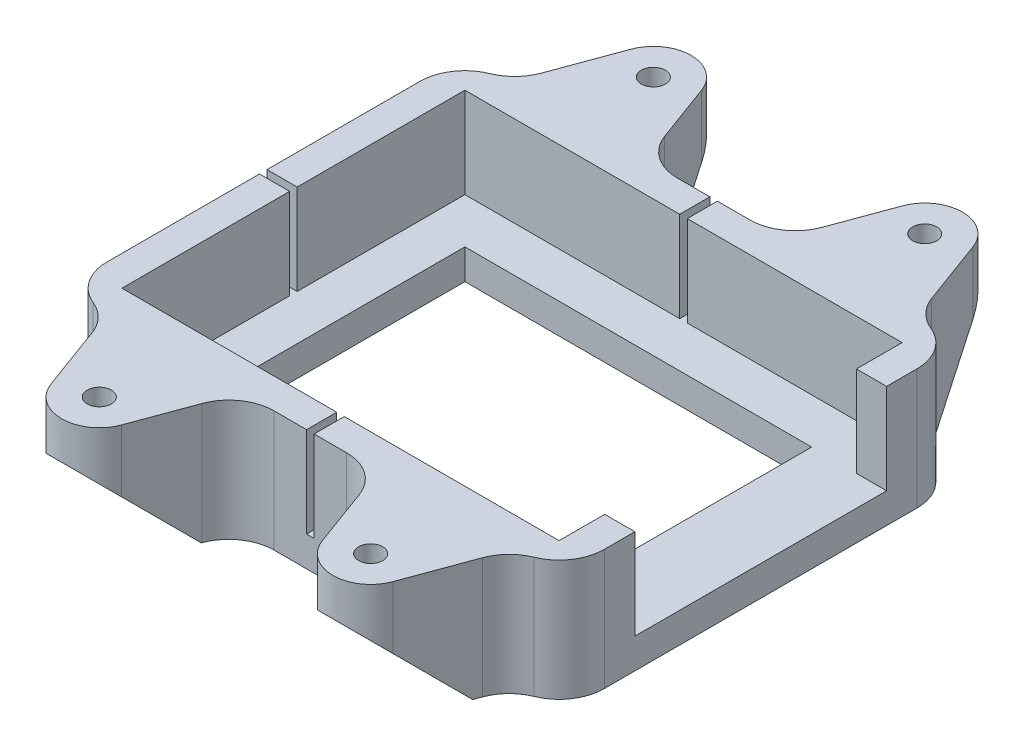
SolidWorks part; units mm, degrees
ref_plane "前视基准面" through (0, 0, 0) normal (0, 0, 1) x (1, 0, 0)
ref_plane "上视基准面" through (0, 0, 0) normal (0, 1, 0) x (1, 0, 0)
ref_plane "右视基准面" through (0, 0, 0) normal (1, 0, 0) x (0, 0, -1)
other "Configuration Table"
sketch "草图1" plane through (0, 0, 0) normal (0, 1, 0) x (1, 0, 0)
  line L0 (-33, 49.5) -> (33, 49.5)
  line L1 (-29, 45.5) -> (29, 45.5)
  line L2 (-29, 45.5) -> (-29, 0)
  line L3 (-29, 0) -> (29, 0)
  line L4 (29, 45.5) -> (29, 0)
  line L5 (33, 49.5) -> (33, -4)
  line L6 (-33, -4) -> (33, -4)
  line L7 (-33, 49.5) -> (-33, -4)
  line L8 (-23, 39.5) -> (23, 39.5)
  line L9 (23, 39.5) -> (23, 6)
  line L10 (-23, 6) -> (23, 6)
  line L11 (-23, 39.5) -> (-23, 6)
  point P4 (0, 0)
  dimension "D1" = 58
  dimension "D2" = 45.5
  dimension "D3" = 4
  dimension "D4" = 6
extrude "凸台-拉伸1" add sketch "草图1" along normal blind 4 contours L0 L7 L6 L5 L1 L4 L3 L2 | L4 L1 L2 L3 L11 L8 L9 L10 region at (0, 0, -48.6504) region at (0, 0, -44.7628)
extrude "凸台-拉伸2" add sketch "草图1<4>" along normal blind 12 from surface contours L0 L7 L6 L5 L1 L4 L3 L2 region at (0, 0, -48.6504) starting at face at (0, 4, -22.75)
sketch "草图1<4>" plane through (0, 0, 0) normal (0, 1, 0) x (1, 0, 0) same geometry as "草图1"
sketch "草图2" plane through (0, 16, 0) normal (0, 1, 0) x (1, 0, 0)
  line L0 (0, 49.5) -> (0, 0) construction
  line L1 (33, 49.5) -> (-33, 49.5) construction
  line L2 (29, 0) -> (-29, 0) construction
  line L3 (-33, 22.75) -> (33, 22.75) construction
  line L4 (-33, -4) -> (-33, 49.5) construction
  line L5 (33, -4) -> (33, 49.5) construction
  line L6 (13.3066, 61.224) -> (9, 49.5)
  line L7 (9, 49.5) -> (27, 49.5)
  line L8 (27, 49.5) -> (22.6934, 61.224)
  line L9 (-27, 49.5) -> (-22.6934, 61.224)
  line L10 (-9, 49.5) -> (-27, 49.5)
  line L11 (-13.3066, 61.224) -> (-9, 49.5)
  line L12 (-13.3066, -15.724) -> (-9, -4)
  line L13 (-9, -4) -> (-27, -4)
  line L14 (-27, -4) -> (-22.6934, -15.724)
  line L15 (27, -4) -> (22.6934, -15.724)
  line L16 (9, -4) -> (27, -4)
  line L17 (13.3066, -15.724) -> (9, -4)
  circle A1 centre (18, 59.5) radius 1.6
  arc A3 (22.6934, 61.224) -> (13.3066, 61.224) centre (18, 59.5) ccw
  arc A4 (-22.6934, 61.224) -> (-13.3066, 61.224) centre (-18, 59.5) cw
  circle A5 centre (-18, 59.5) radius 1.6
  circle A6 centre (-18, -14) radius 1.6
  arc A7 (-22.6934, -15.724) -> (-13.3066, -15.724) centre (-18, -14) ccw
  arc A8 (22.6934, -15.724) -> (13.3066, -15.724) centre (18, -14) cw
  circle A9 centre (18, -14) radius 1.6
  point P0 (0, 0)
  point P1 (27.3409, 51)
  dimension "D1" = 10
  dimension "D2" = 3.2
  dimension "D3" = 10
  dimension "D4" = 18
  dimension "D5" = 18
extrude "凸台-拉伸3" add sketch "草图2" against normal blind 5
chamfer "倒角1" distance 15 angle 45 4 edges at (18, 11, 4) (-18, 11, 4) (18, 11, -49.5) (-18, 11, -49.5)
sketch "草图4" plane through (0, 0, 0) normal (0, -1, 0) x (1, 0, 0)
  circle A0 centre (-18, 14) radius 3.3
  circle A1 centre (18, 14) radius 3.3
  circle A2 centre (18, -59.5) radius 3.3
  circle A3 centre (-18, -59.5) radius 3.3
  dimension "D1" = 6.6
extrude "切除-拉伸1" cut sketch "草图4" against normal blind 11
sketch "草图5" plane through (0, 16, 0) normal (0, 1, 0) x (1, 0, 0)
  line L0 (0, 49.5) -> (0, 45.5)
  line L1 (9, 49.5) -> (-9, 49.5) construction
  line L2 (29, 45.5) -> (-29, 45.5) construction
  line L3 (29, 22.75) -> (33, 22.75)
  line L4 (29, 0) -> (29, 45.5) construction
  line L5 (33, -4) -> (33, 49.5) construction
  line L6 (0, 0) -> (0, -4)
  line L7 (9, -4) -> (-9, -4) construction
  line L8 (-29, 22.75) -> (-33, 22.75)
  line L9 (-29, 0) -> (-29, 45.5) construction
  line L10 (-33, -4) -> (-33, 49.5) construction
extrude "切除-拉伸-薄壁1" cut sketch "草图5" against normal up to surface (12 mm away) thin up to face at (0, 4, -22.75) thin type two direction wall 0.5 second wall 0.5
fillet "圆角1" radius 6 4 edges at (-33, 8, -49.5) (-33, 8, 4) (33, 8, -49.5) (33, 8, 4)
fillet "圆角2" radius 6 8 edges at (9, 8, -49.5) (-9, 8, -49.5) (-9, 8, 4) (9, 8, 4) (-27, 8, 4) (27, 8, 4) (27, 8, -49.5) (-27, 8, -49.5)
sketch "草图6" plane through (33, 0, 0) normal (1, 0, 0) x (0, 0, -1)
  line L0 (2, 16) -> (22.25, 16) construction
  line L1 (6.0519, 16) -> (39.4481, 16)
  line L2 (6.0519, 16) -> (6.0519, 4)
  line L3 (6.0519, 4) -> (39.4481, 4)
  line L4 (39.4481, 16) -> (39.4481, 4)
  line L5 (39.5, 4) -> (6, 4) construction
  line L6 (22.75, 0) -> (22.75, 4) construction
  line L8 (43.5, 0) -> (2, 0) construction
extrude "切除-拉伸2" cut sketch "草图6" against normal blind 8
